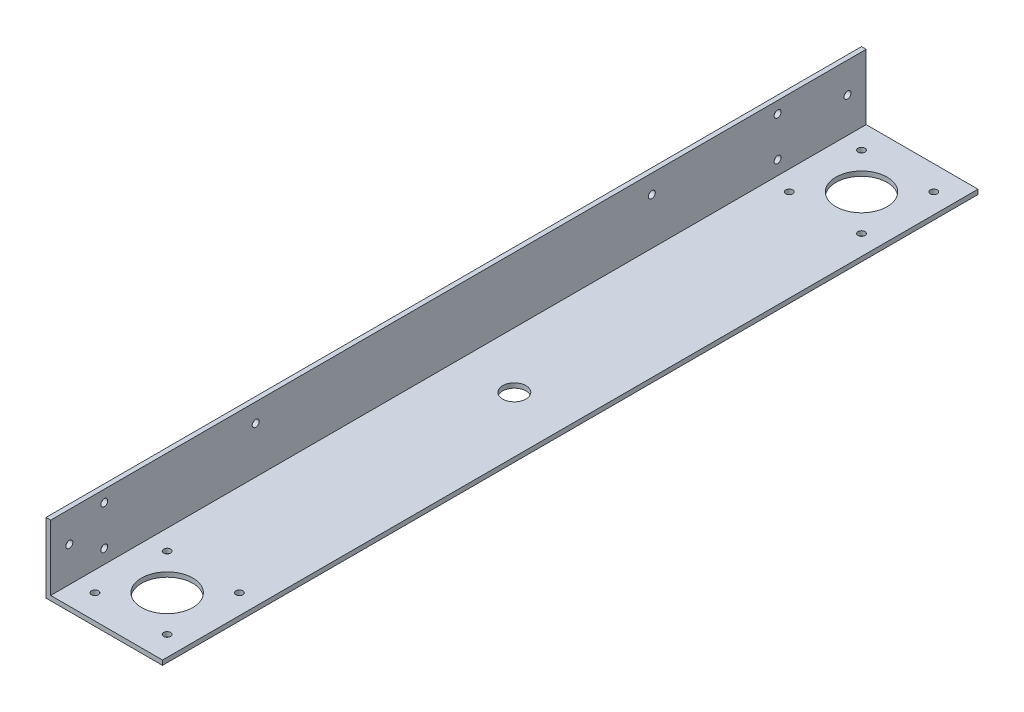
SolidWorks part; units mm, degrees
ref_plane "Front Plane" through (0, 0, 0) normal (0, 0, 1) x (1, 0, 0)
ref_plane "Top Plane" through (0, 0, 0) normal (0, 1, 0) x (1, 0, 0)
ref_plane "Right Plane" through (0, 0, 0) normal (1, 0, 0) x (0, 0, -1)
sketch "Sketch1" plane through (0, 0, 0) normal (0, 0, 1) x (1, 0, 0)
  line L0 (0, 0) -> (0, 30)
  line L1 (0, 30) -> (2, 30)
  line L2 (2, 30) -> (2, 2)
  line L3 (2, 2) -> (50, 2)
  line L4 (50, 2) -> (50, 0)
  line L5 (50, 0) -> (0, 0)
extrude "Boss-Extrude1" add sketch "Sketch1" along normal blind 350
sketch "Sketch6" plane through (0, 2, 0) normal (0, 1, 0) x (1, 0, 0)
  circle A0 centre (41.5, -339.5) radius 1.5
  circle A1 centre (10.5, -308.5) radius 1.5
  circle A2 centre (10.5, -339.5) radius 1.5
  circle A3 centre (41.5, -308.5) radius 1.5
extrude "Cut-Extrude3" cut sketch "Sketch6" against normal through all
sketch "Sketch7" plane through (0, 2, 0) normal (0, 1, 0) x (1, 0, 0)
  circle A0 centre (26, -324) radius 11
extrude "Cut-Extrude4" cut sketch "Sketch7" against normal through all
sketch "Sketch8" plane through (0, 0, 0) normal (0, -1, 0) x (-1, 0, 0)
  circle A0 centre (-26, -26) radius 11
extrude "Cut-Extrude5" cut sketch "Sketch8" against normal through all
sketch "Sketch9" plane through (0, 0, 0) normal (0, -1, 0) x (1, 0, 0)
  circle A0 centre (41.5, 41.5) radius 1.5
  circle A1 centre (10.5, 41.5) radius 1.5
  circle A2 centre (10.5, 10.5) radius 1.5
  circle A3 centre (41.5, 10.5) radius 1.5
extrude "Cut-Extrude6" cut sketch "Sketch9" against normal through all
sketch "Sketch10" plane through (0, 0, 0) normal (0, -1, 0) x (1, 0, 0)
  circle A0 centre (26, 175) radius 5
extrude "Cut-Extrude7" cut sketch "Sketch10" against normal through all
hole_wizard "Ø3.0 (3) Diameter Hole1" positions "Sketch11" profile "Sketch12" hole size "Ø3.0" standard "ISO"
sketch "Sketch11" plane through (0, 141.68, 221.138) normal (-1, 0, 0) x (0, 0, 1)
  point P0 (105.862, -133.68)
  point P1 (120.862, -124.68)
  point P2 (105.862, -116.68)
sketch "Sketch12" plane through (0, 8, 327) normal (0, 1, 0) x (0, 0, 1)
  line L0 (0, 0) -> (0, 1.999)
  line L1 (0, 1.999) -> (1.5, 1.999)
  line L2 (1.5, 1.999) -> (1.5, 0)
  line L3 (1.5, 0) -> (0, 0)
  line L4 (0, -6.35) -> (0, 107.95) construction
  dimension "Thru Hole Dia." = 3
  dimension "Thru Hole Depth" = 1.999
hole_wizard "Ø3.0 (3) Diameter Hole2" positions "Sketch13" profile "Sketch14" hole
sketch "Sketch13" plane through (0, 141.68, 221.138) normal (-1, 0, 0) x (0, 0, 1)
  point P0 (-183.138, -133.68)
  point P1 (-213.138, -124.68)
  point P2 (-183.138, -116.68)
sketch "Sketch14" plane through (0, 8, 38) normal (0, 1, 0) x (0, 0, 1)
  line L0 (0, 0) -> (0, 1.999)
  line L1 (0, 1.999) -> (1.5, 1.999)
  line L2 (1.5, 1.999) -> (1.5, 0)
  line L3 (1.5, 0) -> (0, 0)
  line L4 (0, -6.35) -> (0, 107.95) construction
  dimension "Thru Hole Dia." = 3
  dimension "Thru Hole Depth" = 1.999
sketch "Sketch15" plane through (0, 0, 0) normal (-1, 0, 0) x (0, 0, 1)
  circle A0 centre (262, 22) radius 1.5
  circle A1 centre (92, 22) radius 1.5
extrude "Cut-Extrude8" cut sketch "Sketch15" against normal through all
